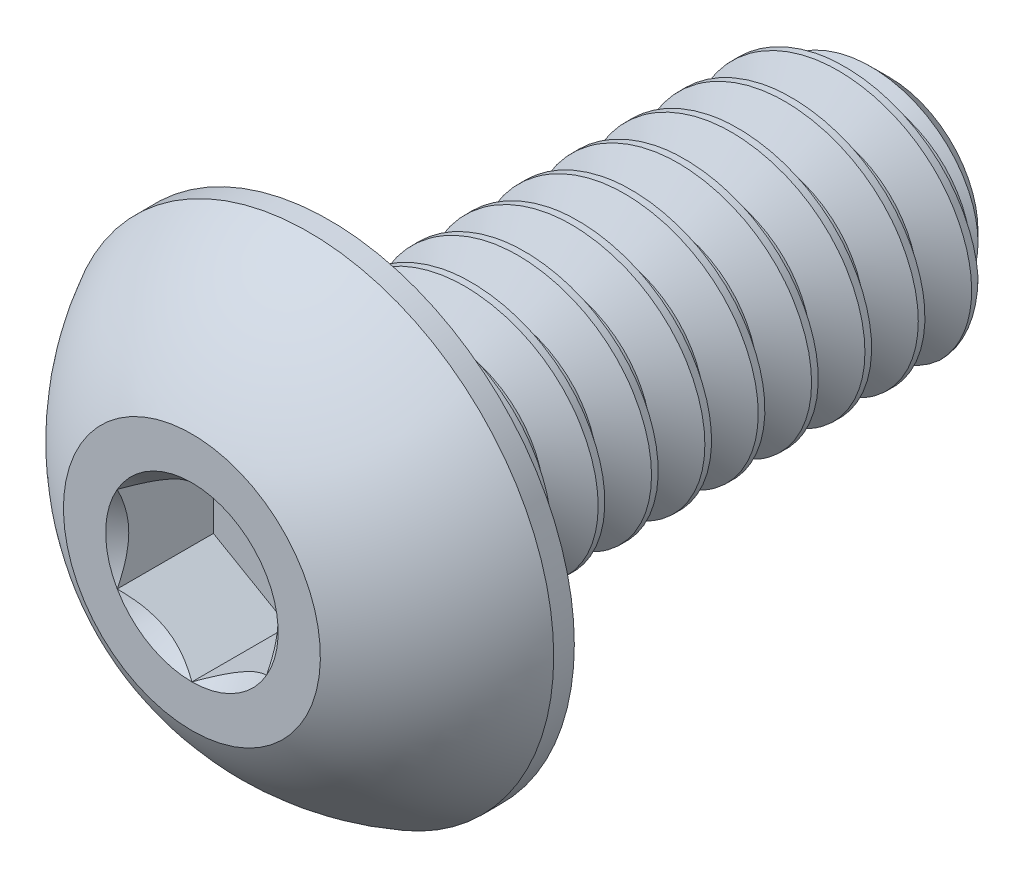
SolidWorks part; units mm, degrees
ref_plane "Front" through (0, 0, 0) normal (0, 0, 1) x (1, 0, 0)
ref_plane "Top" through (0, 0, 0) normal (0, 1, 0) x (1, 0, 0)
ref_plane "Right" through (0, 0, 0) normal (1, 0, 0) x (0, 0, -1)
sketch "Sketch1" plane through (0, 0, 0) normal (1, 0, 0) x (0, 0, -1)
  line L2 (1.1684, 1.0922) -> (5.9309, 1.0922)
  line L3 (5.9309, 1.0922) -> (5.9309, 0)
  line L4 (5.9309, 0) -> (1.1684, 0)
  line L6 (0.9931, 2.0828) -> (1.1684, 2.0828) construction
  line L7 (5.9309, 1.0922) -> (5.9309, -1.0922) construction
  line L8 (0, 0) -> (1.1684, 0) construction
  line L9 (1.1684, 2.0828) -> (1.1684, -2.0828) construction
  line L11 (1.1684, 1.0922) -> (1.1684, 0)
  line L13 (0, 0.635) -> (0, -0.635) construction
  line L14 (0, 0.635) -> (0, 1.0922) construction
  arc A3 (0, 1.0922) -> (0.9931, 2.0828) centre (2.08, 0) cw construction
  dimension "D1" = 0.1753
  dimension "Head Ht" = 1.1684
  dimension "Head Dia" = 4.1656
  dimension "Dia" = 2.1844
  dimension "Lg" = 4.7625
  dimension "Hex" = 1.27
revolve "Revolve1" add sketch "Sketch1" angle 360 mid plane about L4
sketch "Sketch3" plane through (0, 0, -5.9309) normal (0, 0, -1) x (-1, 0, 0)
  circle A0 centre (0, 0) radius 1.0922
curve "Helix/Spiral1" pitch 0.4536 height 5.2161 radius 1.0922 centre (0, 0, -5.9309) axis (0, 0, 1) start towards (0, 1, 0)
sketch "Sketch2" plane through (0, 0, 0) normal (1, 0, 0) x (0, 0, -1)
  line L0 (5.9309, 1.0922) -> (6.3278, 1.0922)
  line L1 (6.3278, 1.0922) -> (6.1577, 0.7976)
  line L2 (6.1577, 0.7976) -> (6.101, 0.7976)
  line L3 (6.101, 0.7976) -> (5.9309, 1.0922)
  line L4 (6.0159, 0.9449) -> (6.2427, 0.9449) construction
  dimension "D1" = 60
  dimension "D2" = 0.0567
  dimension "D3" = 0.2268
chamfer "Chamfer1" distance 0.3402 angle 45 1 edges at (0, 1.0922, -5.9309)
sweep "Cut-Sweep1" cut profiles "Sketch2" path "Helix/Spiral1"
sketch "Sketch7" plane through (0, 0, 0) normal (1, 0, 0) x (0, 0, -1)
  line L6 (0.9931, 2.0828) -> (1.1684, 2.0828) construction
  line L8 (0, 0) -> (1.1684, 0) construction
  line L11 (1.1684, 2.0828) -> (1.1684, -2.0828) construction
  line L12 (0.9931, 2.0828) -> (1.1684, 2.0828)
  line L13 (0, 0) -> (1.1684, 0)
  line L14 (0, 0.635) -> (0, -0.635) construction
  line L15 (1.1684, 2.0828) -> (1.1684, 0)
  line L16 (0, 1.0922) -> (0, 0)
  arc A2 (0.9931, 2.0828) -> (0, 1.0922) centre (2.08, 0) ccw construction
  arc A3 (0.9931, 2.0828) -> (0, 1.0922) centre (2.08, 0) ccw
revolve "Revolve2" add sketch "Sketch7" angle 360 mid plane about L13
sketch "Sketch5" plane through (0, 0, 0) normal (0, 0, 1) x (1, 0, 0)
  line L1 (0.635, -0.3666) -> (0.635, 0.3666)
  line L2 (0.635, 0.3666) -> (0, 0.7332)
  line L3 (0, 0.7332) -> (-0.635, 0.3666)
  line L4 (-0.635, 0.3666) -> (-0.635, -0.3666)
  line L5 (-0.635, -0.3666) -> (0, -0.7332)
  line L6 (0, -0.7332) -> (0.635, -0.3666)
  circle A0 centre (0, 0) radius 0.635 construction
extrude "Cut-Extrude2" cut sketch "Sketch5" against normal blind 0.8179
sketch "Sketch6" plane through (0, 0, 0) normal (0, 0, 1) x (1, 0, 0)
  circle A0 centre (0, 0) radius 0.7332
extrude "Cut-Extrude3" cut sketch "Sketch6" against normal blind 0.8179 draft 45
sketch "Sketch9" [suppressed] plane through (0, 0, -1.1684) normal (0, 0, 1) x (1, 0, 0)
  circle A2 centre (0, 0) radius 1.0922
extrude "Boss-Extrude2" [suppressed] add sketch "Sketch9" against normal offset from surface (6.35 mm away) 31.75 up to face at (0, 0.752, -5.9309)
sketch "Sketch10" plane through (0, 0, 0) normal (1, 0, 0) x (0, 0, -1)
  line L0 (5.9309, 1.0922) -> (5.9309, -1.0922) construction
  point P0 (5.2505, -1.0922)
  dimension "D1" = 0.6804
equation "\"D3@Helix/Spiral1\" = \"Lg@Sketch1\" + \"D4@Helix/Spiral1\""
equation "\"D2@Sketch2\" = \"D4@Helix/Spiral1\" * .125"
equation "\"D3@Sketch2\" = \"D4@Helix/Spiral1\" * .5"
equation "\"D1@Chamfer1\" = \"D4@Helix/Spiral1\" * .75"
equation "\"D1@Cut-Extrude2\" = \"Head Ht@Sketch1\" * .7"
equation "\"D1@Sketch1\" = \"Head Ht@Sketch1\" * .15"
equation "\"D1@Sketch10\" = \"D4@Helix/Spiral1\" * 1.5"
equation "\"D1@Cut-Extrude3\" = \"D1@Cut-Extrude2\""
